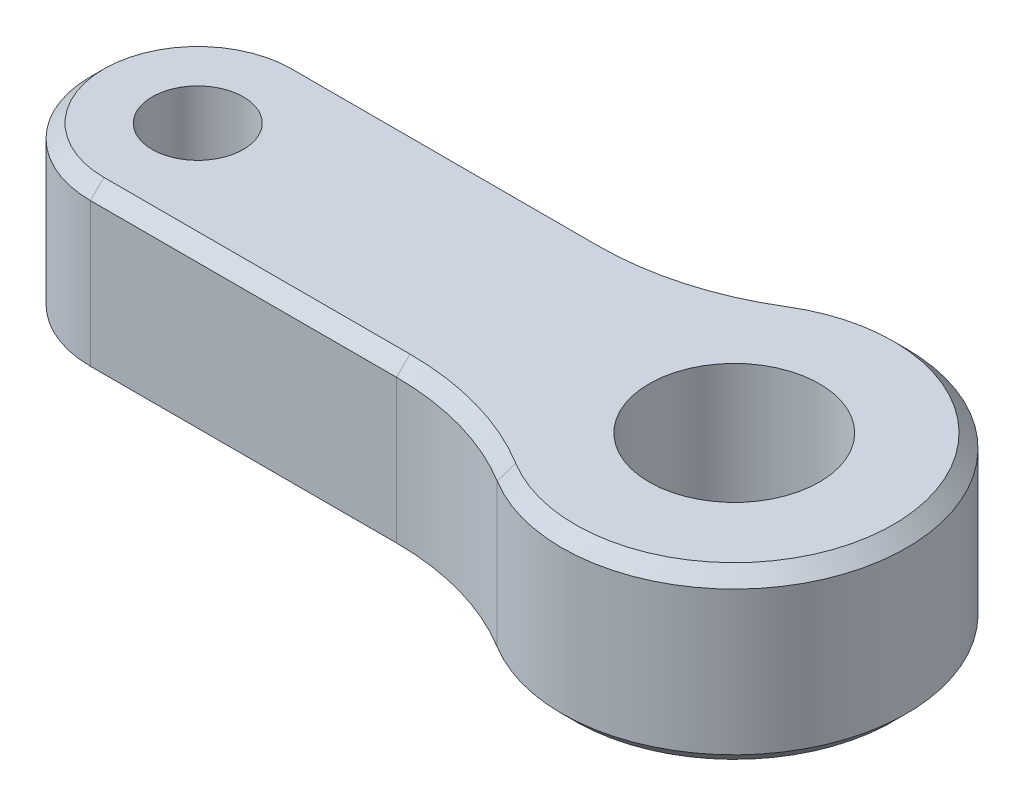
SolidWorks part; units mm, degrees
ref_plane "Front Plane" through (0, 0, 0) normal (0, 0, 1) x (1, 0, 0)
ref_plane "Top Plane" through (0, 0, 0) normal (0, 1, 0) x (1, 0, 0)
ref_plane "Right Plane" through (0, 0, 0) normal (1, 0, 0) x (0, 0, -1)
sketch "Sketch2" plane through (0, 0, 0) normal (0, 1, 0) x (1, 0, 0)
  line L0 (0, 0) -> (20, 0) construction
  line L1 (0, 4) -> (20, 4)
  line L2 (0, -4) -> (20, -4)
  arc A0 (0, 4) -> (0, -4) centre (0, 0) ccw
  arc A1 (20, -4) -> (20, 4) centre (20, 0) ccw
  circle A2 centre (0, 0) radius 1.7
  circle A3 centre (20, 0) radius 3.175
  circle A4 centre (20, 0) radius 6.425
  point P3 (10, 0)
  dimension "D2" = 3.4
  dimension "D4" = 6.35
  dimension "D5" = 12.85
  dimension "D1" = 20
  dimension "D3" = 8
extrude "Boss-Extrude1" add sketch "Sketch2" along normal blind 6.35 contours A2 A4 L1 A0 L2 | L1 A4 A3 L2 A1 | L2 A4 L1 A1 region at (5.8039, 0, 0) region at (22.0617, 0, -5.9032) region at (17.486, 0, -3.8686)
fillet "Fillet1" radius 10 2 edges at (14.972, 3.175, 4) (14.972, 3.175, -4)
chamfer "Chamfer2" distance 0.5 angle 45 12 edges at (14.1274, 0, 4.3762) (5.7052, 0, 4) (26.425, 0, 0) (-4, 0, 0) (14.1274, 0, -4.3762) (5.7052, 0, -4) (14.1274, 6.35, 4.3762) (5.7052, 6.35, 4) (26.425, 6.35, 0) (-4, 6.35, 0) (14.1274, 6.35, -4.3762) (5.7052, 6.35, -4)
equation "\"D5@Sketch2\"=\"D4@Sketch2\"+6.5mm"
